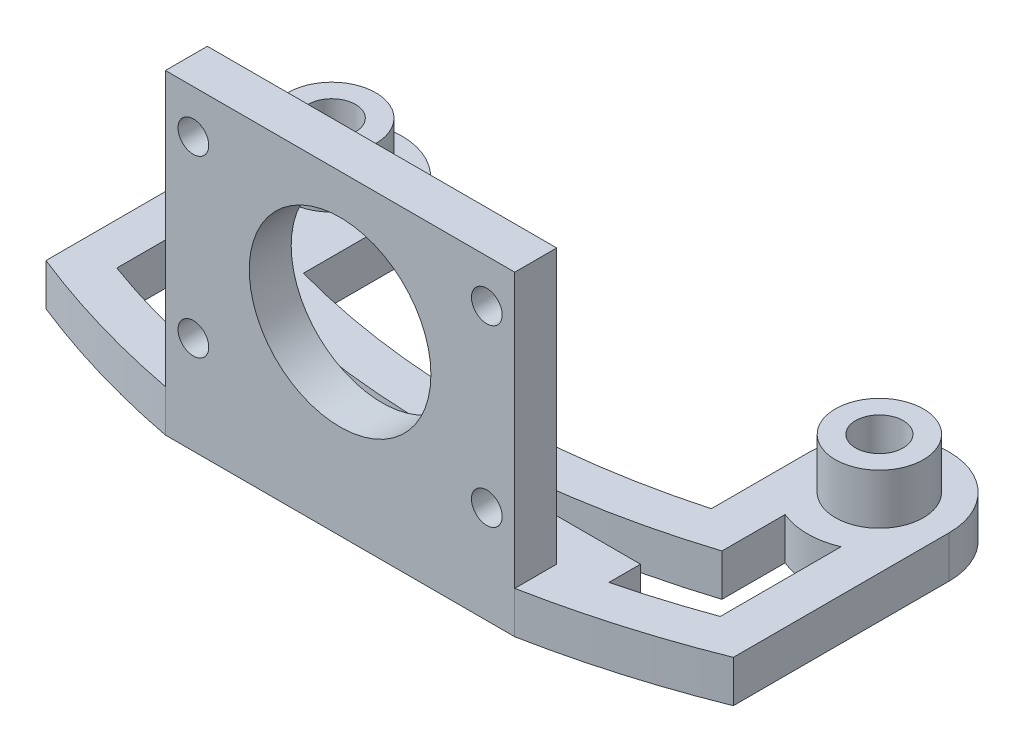
SolidWorks part; units mm, degrees
ref_plane "Front Plane" through (0, 0, 0) normal (0, 0, 1) x (1, 0, 0)
ref_plane "Top Plane" through (0, 0, 0) normal (0, 1, 0) x (1, 0, 0)
ref_plane "Right Plane" through (0, 0, 0) normal (1, 0, 0) x (0, 0, -1)
sketch "Sketch1" plane through (0, 0, 0) normal (0, 1, 0) x (1, 0, 0)
  line L0 (0, -1000) -> (0, 49000) construction
  line L1 (14.5959, -46) -> (14.5959, -62)
  line L2 (-12.5, -62) -> (12.5, -62)
  line L3 (-12.5, -62) -> (-12.5, -65)
  line L4 (-12.5, -65) -> (12.5, -65)
  line L5 (12.5, -62) -> (12.5, -65)
  line L6 (-12.5, -62) -> (12.5, -65) construction
  line L7 (-12.5, -65) -> (12.5, -62) construction
  line L8 (-24.5959, -46) -> (-24.5959, -61.4515)
  line L9 (24.5959, -46) -> (24.5959, -61.4515)
  line L12 (-14.5959, -46) -> (-14.5959, -62)
  circle A0 centre (0, 0) radius 50 construction
  circle A1 centre (-19.5959, -46) radius 3.15
  circle A2 centre (0, -50) radius 3.15 construction
  circle A3 centre (19.5959, -46) radius 3.15
  arc A4 (-24.5959, -49.1939) -> (24.5959, -49.1939) centre (0, 0) ccw
  circle A5 centre (-19.5959, -46) radius 5
  circle A6 centre (19.5959, -46) radius 5
  circle A7 centre (-19.5959, -46) radius 1.7
  circle A8 centre (19.5959, -46) radius 1.7
  arc A9 (-24.5959, -61.4515) -> (-12.5, -65) centre (0, 0) ccw
  arc A10 (12.5, -65) -> (24.5959, -61.4515) centre (0, 0) ccw
  point P16 (0, -63.5)
  dimension "D1" = 100
  dimension "D2" = 6.3
  dimension "D4" = 110
  dimension "D5" = 3.4
  dimension "D3" = 20
  dimension "D6" = 25
  dimension "D7" = 3
  dimension "D8" = 65
extrude "Boss-Extrude2" add sketch "Sketch1" against normal blind 3 contours L8 A9 L3 L2 L12 A4 | A1 A7 | A5 A1 | A5 L8 A4 | A5 A4 L12 | A4 L12 L2 L1 | L5 L2 L3 L4 | L5 A10 L9 A4 L1 L2 | A4 A6 L1 | A6 A3 | L9 A6 A4 | A3 A8 region at (16.2515, 0, 50.8752) region at (19.5959, 0, 41.1414) region at (0, 0, 57.8068) region at (23.9572, 0, 48.834) region at (-16.2515, 0, 50.8752) region at (-16.9169, 0, 50.0532) region at (-23.9572, 0, 48.834) region at (0, 0, 63.5) region at (-22.6568, 0, 46) region at (16.535, 0, 46)
extrude "Boss-Extrude3" add sketch "Sketch1<5>" along normal blind 3.6 contours A1 A7 | A3 A8 | L3 L2 L5 L4 region at (-22.6568, 0, 46) region at (16.535, 0, 46)
sketch "Sketch1<5>" plane through (0, 0, 0) normal (0, 1, 0) x (1, 0, 0) same geometry as "Sketch1"
extrude "Boss-Extrude4" add sketch "Sketch1<7>" along normal blind 16 from surface contours L5 L2 L3 L4 region at (0, 0, 63.5) starting at face at (0, 3.6, 63.5)
sketch "Sketch1<7>" plane through (0, 0, 0) normal (0, 1, 0) x (1, 0, 0) same geometry as "Sketch1"
sketch "Sketch2" plane through (0, 0, 65) normal (0, 0, 1) x (1, 0, 0)
  line L0 (-10.5, 4) -> (-10.5, 16.5) construction
  line L1 (0, -1000) -> (0, 49000) construction
  line L2 (10.5, 16.5) -> (10.5, 4) construction
  line L3 (-10.5, 10.25) -> (10.5, 10.25) construction
  circle A0 centre (-10.5, 4) radius 1.1
  circle A1 centre (-10.5, 16.5) radius 1.1
  circle A2 centre (10.5, 4) radius 1.1
  circle A3 centre (10.5, 16.5) radius 1.1
  circle A4 centre (0, 10.25) radius 6.5
  point P15 (0, 0)
  dimension "D2" = 2.2
  dimension "D5" = 13
  dimension "D1" = 12.5
  dimension "D3" = 21
  dimension "D4" = 4
extrude "Cut-Extrude1" cut sketch "Sketch2" against normal up to next
sketch "Sketch3" plane through (0, 0, 0) normal (0, 1, 0) x (1, 0, 0)
  line L229 (-15.5, -61.2605) -> (-15.5, -59)
  line L230 (-15.5, -59) -> (15.5, -59)
  line L231 (15.5, -59) -> (15.5, -61.2605)
  line L232 (21.5959, -59.3862) -> (21.5959, -46)
  line L233 (17.5959, -46) -> (17.5959, -55.2665)
  line L234 (-17.5959, -55.2665) -> (-17.5959, -46)
  line L235 (-21.5959, -46) -> (-21.5959, -59.3862)
  line L236 (-15.5, -61.2605) -> (-15.5, -59)
  line L237 (-15.5, -59) -> (15.5, -59)
  line L238 (15.5, -59) -> (15.5, -61.2605)
  line L239 (21.5959, -59.3862) -> (21.5959, -50.7458)
  line L240 (17.5959, -50.7458) -> (17.5959, -55.2665)
  line L241 (-17.5959, -55.2665) -> (-17.5959, -50.7458)
  line L242 (-21.5959, -50.7458) -> (-21.5959, -59.3862)
  circle A5 centre (-19.5959, -46) radius 5.15
  arc A6 (-21.5959, -50.7458) -> (-17.5959, -50.7458) centre (-19.5959, -46) ccw
  circle A8 centre (19.5959, -46) radius 5.15
  arc A9 (17.5959, -50.7458) -> (21.5959, -50.7458) centre (19.5959, -46) ccw
  arc A163 (-21.5959, -59.3862) -> (-15.5, -61.2605) centre (0, 0) ccw
  arc A164 (15.5, -61.2605) -> (21.5959, -59.3862) centre (0, 0) ccw
  arc A165 (21.5959, -46) -> (17.5959, -46) centre (19.5959, -46) ccw
  arc A166 (-17.5959, -55.2665) -> (17.5959, -55.2665) centre (0, 0) ccw
  arc A167 (-17.5959, -46) -> (-21.5959, -46) centre (-19.5959, -46) ccw
  arc A168 (-21.5959, -59.3862) -> (-15.5, -61.2605) centre (0, 0) ccw
  arc A169 (15.5, -61.2605) -> (21.5959, -59.3862) centre (0, 0) ccw
  arc A171 (-17.5959, -55.2665) -> (17.5959, -55.2665) centre (0, 0) ccw
  dimension "D1" = 3
  dimension "D2" = 2
  dimension "D3" = 2
extrude "Cut-Extrude2" cut sketch "Sketch3" against normal up to next
